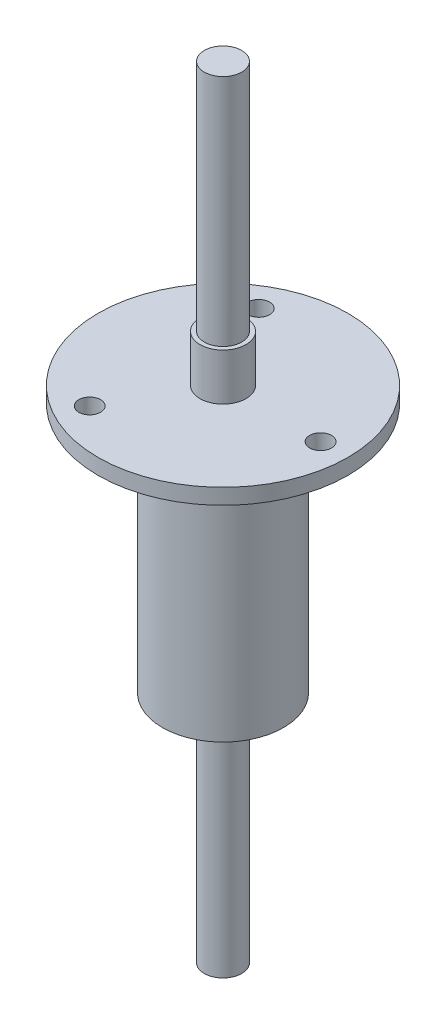
SolidWorks part; units mm, degrees
ref_plane "Front Plane" through (0, 0, 0) normal (0, 0, 1) x (1, 0, 0)
ref_plane "Top Plane" through (0, 0, 0) normal (0, 1, 0) x (1, 0, 0)
ref_plane "Right Plane" through (0, 0, 0) normal (1, 0, 0) x (0, 0, -1)
sketch "Sketch1" plane through (0, 0, 0) normal (1, 0, 0) x (0, 0, -1)
  line L0 (0, 23.9311) -> (0, -15.9842) construction
  line L1 (0, 20.05) -> (2.95, 20.05)
  line L2 (2.95, 20.05) -> (2.95, 14.05)
  line L3 (2.95, 14.05) -> (16, 14.05)
  line L4 (16, 14.05) -> (16, 12.05)
  line L5 (16, 12.05) -> (7.75, 12.05)
  line L6 (7.75, 12.05) -> (7.75, -20.05)
  line L7 (7.75, -20.05) -> (0, -20.05)
  line L8 (0, -20.05) -> (0, 20.05)
  dimension "D1" = 5.9
  dimension "D2" = 34.1
  dimension "D3" = 2
  dimension "D4" = 6
  dimension "D5" = 32
  dimension "D6" = 15.5
revolve "Revolve1" add sketch "Sketch1" angle 360 about L0
sketch "Sketch2" plane through (0, 14.05, 0) normal (0, 1, 0) x (1, 0, 0)
  circle A0 centre (0, 0) radius 12.5 construction
  circle A1 centre (12.5, 0) radius 1.4
  circle A2 centre (-6.25, -10.8253) radius 1.4
  circle A3 centre (-6.25, 10.8253) radius 1.4
  point P11 (0, 0)
  dimension "D1" = 3
  dimension "D2" = 25
  dimension "D3" = 2.8
extrude "Cut-Extrude1" cut sketch "Sketch2" against normal through all both
sketch "Sketch3" plane through (0, 0, 0) normal (0, 1, 0) x (1, 0, 0)
  circle A0 centre (0, 0) radius 2.4
  dimension "D1" = 4.8
extrude "Boss-Extrude1" add sketch "Sketch3" along normal mid plane 100
split "Split1" bodies to split 103 resulting bodies 104 105 split by face at (12.5, 14.05, 1.4)
